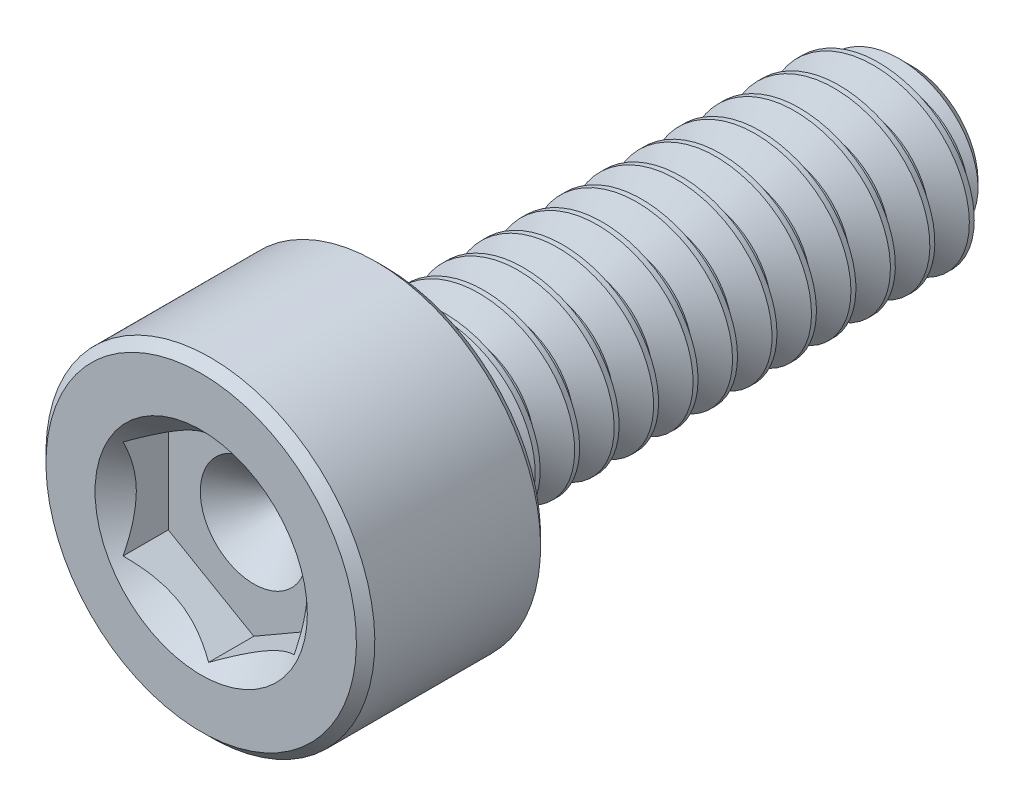
SolidWorks part; units mm, degrees
ref_plane "Front Plane" through (0, 0, 0) normal (0, 0, 1) x (1, 0, 0)
ref_plane "Top Plane" through (0, 0, 0) normal (0, 1, 0) x (1, 0, 0)
ref_plane "Right Plane" through (0, 0, 0) normal (1, 0, 0) x (0, 0, -1)
sketch "Sketch1" plane through (0, 0, 0) normal (1, 0, 0) x (0, 0, -1)
  line L0 (-2.7, 0) -> (2.7, 0) construction
  line L1 (2.7, 0) -> (2.7, 0.5051) construction
  line L2 (2.7, 0.5051) -> (2.5051, 0.7) construction
  line L3 (2.5051, 0.7) -> (2.475, 0.7) construction
  line L4 (2.475, 0.7) -> (-1.3, 0.7) construction
  line L5 (-1.3, 0.7) -> (-1.3, 1.25) construction
  line L6 (-1.3, 1.25) -> (-2.7, 1.25) construction
  line L7 (-2.7, 1.25) -> (-2.7, 0) construction
  line L8 (2.7, 0.5051) -> (2.7, 0.7) construction
  line L9 (2.6812, 0.7325) -> (2.8312, 0.4727) construction
  line L10 (2.8312, 0.4727) -> (2.9812, 0.7325) construction
  line L11 (2.9812, 0.7325) -> (2.6812, 0.7325) construction
  line L12 (2.8312, 0.7325) -> (2.8312, 0.7) construction
  line L13 (2.8312, 0.4727) -> (2.8312, 0.5051) construction
  line L14 (2.8125, 0.5051) -> (2.85, 0.5051) construction
  line L15 (2.7, 0.7) -> (2.9625, 0.7) construction
  line L16 (2.6906, 0.7162) -> (2.9719, 0.7162) construction
  line L17 (2.7, 0) -> (2.7, -0.7) construction
  line L18 (-1.37, 1.25) -> (-1.3, 1.18) construction
  line L19 (-2.63, 1.25) -> (-2.7, 1.18) construction
  line L20 (-1.3, 0.7) -> (-1.3, 0) construction
  line L21 (-1.3, 0.35) -> (0.0333, 0.35) construction
  line L22 (0.0333, 0.35) -> (1.3667, 0.35) construction
  line L23 (1.3667, 0.35) -> (2.7, 0.35) construction
  line L24 (0.0333, 0.35) -> (0.0333, 0.7) construction
  line L25 (0.0333, 0.7) -> (0.0333, 1.25) construction
  line L26 (1.3667, 0.35) -> (1.3667, 1.25) construction
  point P0 (-2.7, 0.65)
  point P3 (1.95, 0.7)
  point P4 (0, 0)
  point P18 (1.3667, 0.7)
  point P22 (2.8312, 0.5051)
  point P24 (2.475, 0.7)
  point P25 (2.8312, 0.7)
  point P28 (2.8312, 0.7162)
  point P29 (1.95, -0.7)
  point P30 (0.0333, 0.7)
  point P31 (-2, 1.25)
  point P37 (-1.545, 1.25)
  point P38 (-2.595, 1.25)
  point P45 (0.0333, 0.35)
  point P46 (1.3667, 0.35)
  dimension "D2" = 0.0375
  dimension "D7" = 0.07
  dimension "D8" = 0.07
  dimension "D9" = 0.07
  dimension "D10" = 0.035
  dimension "D11" = 0.175
  dimension "Drive Size" = 1.3
  dimension "Head Diameter" = 2.5
  dimension "Head Height" = 1.4
  dimension "Thread Pitch" = 0.3
  dimension "Thread Dia" = 1.4
  dimension "Length" = 4
  dimension "D12" = 0.225
  dimension "D4" = 0.75
  dimension "D3" = 45
sketch "Sketch2" plane through (0, 0, 0) normal (1, 0, 0) x (0, 0, -1)
  line L0 (-2.7, 0) -> (-2.7, 1.18)
  line L1 (-2.63, 1.25) -> (-1.37, 1.25)
  line L2 (-1.3, 1.18) -> (-1.3, 0.77)
  line L4 (2.5051, 0.7) -> (2.7, 0.5051)
  line L5 (2.7, 0.5051) -> (2.7, 0)
  line L6 (-1.3, 1.25) -> (-2.7, 1.25) construction
  line L7 (2.7, 0) -> (-2.7, 0)
  line L8 (-2.63, 1.25) -> (-2.7, 1.18) construction
  line L10 (-2.63, 1.25) -> (-2.7, 1.18)
  line L14 (-1.37, 1.25) -> (-1.3, 1.18) construction
  line L16 (-1.37, 1.25) -> (-1.3, 1.18)
  line L17 (-1.3, 0.7) -> (-1.3, 1.25) construction
  line L19 (-1.23, 0.7) -> (2.5051, 0.7)
  line L20 (2.475, 0.7) -> (-1.3, 0.7) construction
  arc A1 (-1.3, 0.77) -> (-1.23, 0.7) centre (-1.23, 0.77) ccw
  dimension "D3" = 0.07
revolve "Revolve1" add sketch "Sketch2" angle 360 about L7
sketch "Sketch3" plane through (0, 0, 2.7) normal (0, 0, 1) x (1, 0, 0)
  line L1 (0.65, -0.3753) -> (0.65, 0.3753)
  line L2 (0.65, 0.3753) -> (0, 0.7506)
  line L3 (0, 0.7506) -> (-0.65, 0.3753)
  line L4 (-0.65, 0.3753) -> (-0.65, -0.3753)
  line L5 (-0.65, -0.3753) -> (0, -0.7506)
  line L6 (0, -0.7506) -> (0.65, -0.3753)
  circle A0 centre (0, 0) radius 0.65 construction
  circle A1 centre (0, 0) radius 1.25 construction
  circle A2 centre (0, 0) radius 1.25 construction
  circle A3 centre (0, 0) radius 0.7506 construction
  point P13 (0, 0)
  dimension "D1" = 1.5011
extrude "Cut-Extrude1" cut sketch "Sketch3" against normal offset from surface (0.4 mm away) 1 up to face at (0, 1.18, 1.3)
sketch "Sketch4" plane through (0, 0, 2.7) normal (0, 0, 1) x (1, 0, 0)
  circle A0 centre (0, 0) radius 0.8068
  dimension "D1" = 1.6137
extrude "Cut-Extrude2" cut sketch "Sketch4" against normal up to vertex (0.7 mm away) draft 45 up to point (0, 1.25, 2)
sketch "Sketch11" plane through (0, 0, 0) normal (1, 0, 0) x (0, 0, -1)
  line L0 (-2.7, 0) -> (2.7, 0) construction
  line L1 (-2.7, 0) -> (2.7, 0) construction
  line L2 (-0.55, 0) -> (-0.55, 0.7) construction
  line L3 (2.475, 0.7) -> (-1.3, 0.7) construction
  line L4 (1.95, 0) -> (1.95, 0.7) construction
  line L6 (2.7, 0.5051) -> (2.7, 0.7) construction
  point P2 (-0.55, 0)
  point P3 (1.95, 0)
  dimension "D1" = 0.75
  dimension "D2" = 0.75
sketch "Sketch6" plane through (0, 0, -2.7) normal (0, 0, -1) x (-1, 0, 0)
  circle A0 centre (0, 0) radius 0.7
curve "Helix/Spiral1" pitch 0.3 height 4.3 radius 0.7 centre (0, 0, -2.7) axis (0, 0, 1) start towards (0, 1, 0)
sketch "Sketch10" plane through (0, 0, 0) normal (1, 0, 0) x (0, 0, -1)
  line L0 (-1.23, -1.25) -> (-1.23, 1.25)
  line L5 (-2.7, 0) -> (2.7, 0) construction
  line L6 (-1.23, 0.7) -> (-1.23, -0.7) construction
  point P3 (-1.23, 0)
split "Split1" trim tools "Sketch10" bodies to split 106 resulting bodies 114 115
sketch "Sketch7" plane through (0, 0, 0) normal (1, 0, 0) x (0, 0, -1)
  line L0 (2.6906, 0.7162) -> (2.9719, 0.7162)
  line L1 (2.9719, 0.7162) -> (2.85, 0.5051)
  line L2 (2.85, 0.5051) -> (2.8125, 0.5051)
  line L3 (2.8125, 0.5051) -> (2.6906, 0.7162)
sweep "Cut-Sweep1" cut profiles "Sketch7" path "Helix/Spiral1" align with end faces yes
sketch "Sketch8" plane through (0, 0, 0) normal (1, 0, 0) x (0, 0, -1)
  line L0 (-1.3, 0) -> (-1.3, 0.7)
  line L1 (-1.23, -0.7) -> (-1.23, 0.7) construction
  line L2 (-1.3, 0.7) -> (-1.23, 0.7)
  line L4 (-1.23, 0.7) -> (-0.8259, 0)
  line L5 (-0.8259, 0) -> (-1.3, 0)
  line L6 (2.475, 0.7) -> (-1.3, 0.7) construction
  line L7 (-2.7, 0) -> (2.7, 0) construction
  dimension "D1" = 60
revolve "Revolve2" add sketch "Sketch8" angle 360 about L5
equation "\"D2@Sketch1\" = \"Thread Pitch@Sketch1\" / 8"
equation "\"D4@Helix/Spiral1\" = \"Thread Pitch@Sketch1\""
equation "\"D7@Sketch1\" = \"Head Height@Sketch1\" * .05"
equation "\"D8@Sketch1\"=\"D7@Sketch1\""
equation "\"D9@Sketch1\"=\"D7@Sketch1\""
equation "\"D10@Sketch1\"=\"D7@Sketch1\"/2"
equation "\"D11@Sketch1\"=\"D10@Sketch1\"*5"
equation "\"D4@Sketch1\"=\"Thread Pitch@Sketch1\"*2.5"
equation "\"D12@Sketch1\"=\"Thread Pitch@Sketch1\"*.75"
equation "\"D3@Helix/Spiral1\"=\"Length@Sketch1\"+\"Thread Pitch@Sketch1\""
equation "\"D3@Sketch2\"=\"Thread Dia@Sketch1\"*0.05"
equation "\"D1@Sketch11\"=\"Length@Sketch1\"*0.1875"
equation "\"D2@Sketch11\"=\"D1@Sketch11\""
equation "\"D1@Sketch4\"=\"D1@Sketch3\"*1.075"
